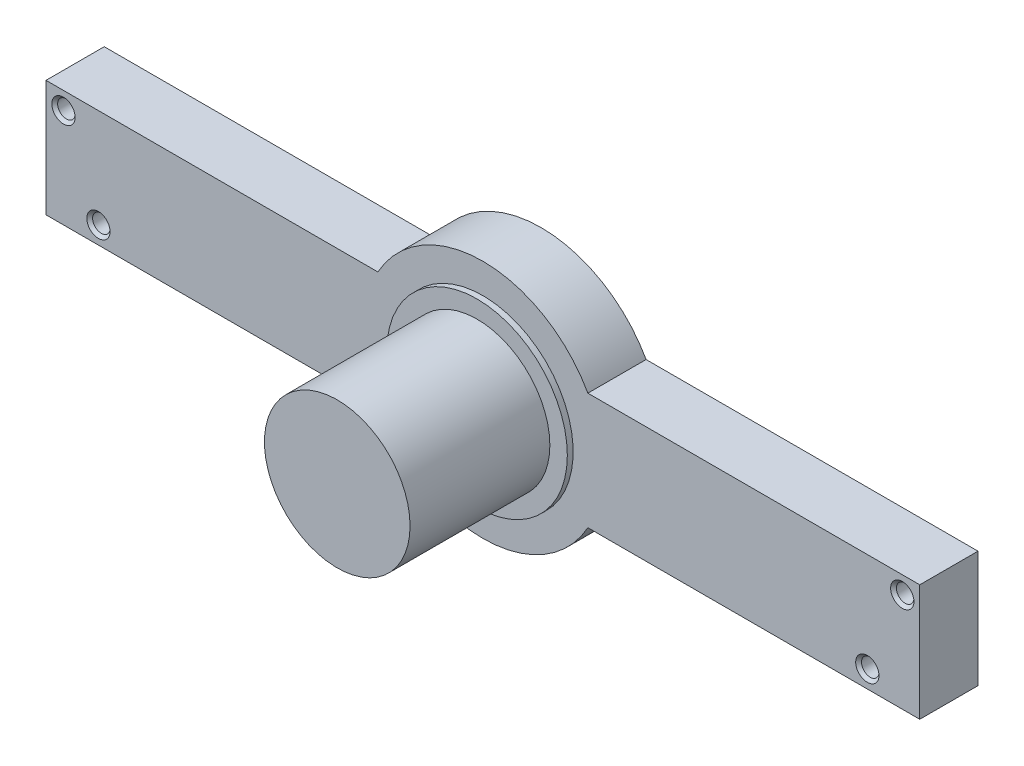
SolidWorks part; units mm, degrees
ref_plane "Płaszczyzna przednia" through (0, 0, 0) normal (0, 0, 1) x (1, 0, 0)
ref_plane "Płaszczyzna górna" through (0, 0, 0) normal (0, 1, 0) x (1, 0, 0)
ref_plane "Płaszczyzna prawa" through (0, 0, 0) normal (1, 0, 0) x (0, 0, -1)
sketch "Szkic1" plane through (0, 0, 0) normal (0, 0, 1) x (1, 0, 0)
  line L1 (-75, -10) -> (75, -10)
  line L2 (-75, -10) -> (-75, 10)
  line L3 (-75, 10) -> (75, 10)
  line L4 (75, -10) -> (75, 10)
  line L5 (-75, -10) -> (75, 10) construction
  line L6 (-75, 10) -> (75, -10) construction
  point P0 (0, 0)
  dimension "D1" = 150
  dimension "D2" = 20
extrude "Dodanie-wyciągnięcie1" add sketch "Szkic1" along normal blind 10
sketch "Szkic2" plane through (0, 0, 10) normal (0, 0, 1) x (1, 0, 0)
  circle A0 centre (0, 0) radius 20.6112
extrude "Dodanie-wyciągnięcie2" add sketch "Szkic2" against normal blind 10
sketch "Szkic3" plane through (0, 0, 10) normal (0, 0, 1) x (1, 0, 0)
  circle A0 centre (0, 0) radius 12.5
  dimension "D1" = 25
extrude "Dodanie-wyciągnięcie5" add sketch "Szkic3" along normal blind 25 contours A0
sketch "Szkic8" plane through (0, 0, 10) normal (0, 0, 1) x (1, 0, 0)
  circle A0 centre (0, 0) radius 15.5
  dimension "D1" = 31
extrude "Dodanie-wyciągnięcie6" add sketch "Szkic8" along normal blind 1
sketch "Szkic9" plane through (0, 0, 0) normal (0, 0, -1) x (-1, 0, 0)
  line L0 (-75, -10) -> (-75, 10) construction
  line L1 (-75, 10) -> (-18.0228, 10) construction
  line L2 (-18.0228, -10) -> (-75, -10) construction
  line L3 (0, 19.25) -> (0, -19.25) construction
  circle A0 centre (-72, 7) radius 1.5
  circle A1 centre (-66, -7) radius 1.5
  circle A2 centre (66, -7) radius 1.5
  circle A3 centre (72, 7) radius 1.5
  dimension "D1" = 3
  dimension "D2" = 3
  dimension "D3" = 3
  dimension "D4" = 3
  dimension "3" = 3
  dimension "9" = 9
extrude "Wytnij-wyciągnięcie1" cut sketch "Szkic9" against normal blind 10
chamfer "Sfazowanie1" distance 0.5 angle 45 4 edges at (-64.5, -7, 10) (-70.5, 7, 10) (64.5, -7, 10) (70.5, 7, 10)
